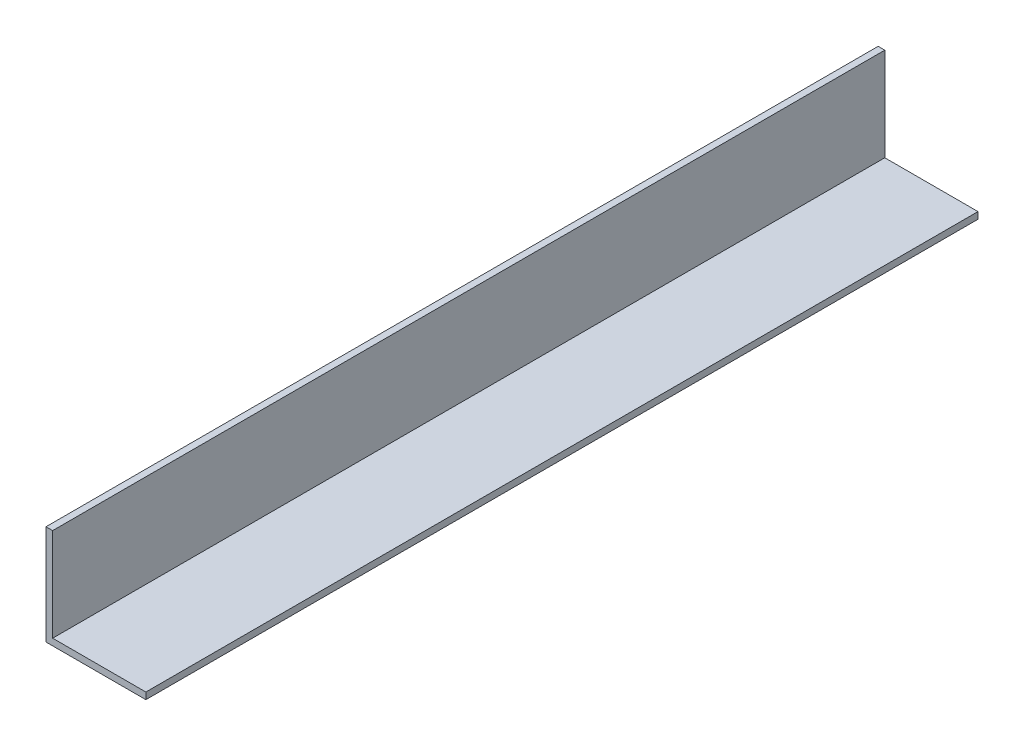
SolidWorks part; units mm, degrees
ref_plane "Front Plane" through (0, 0, 0) normal (0, 0, 1) x (1, 0, 0)
ref_plane "Top Plane" through (0, 0, 0) normal (0, 1, 0) x (1, 0, 0)
ref_plane "Right Plane" through (0, 0, 0) normal (1, 0, 0) x (0, 0, -1)
sketch "Sketch1" plane through (0, 0, 0) normal (0, 0, 1) x (1, 0, 0)
  line L0 (0, 5.6023) -> (0, 35.6023)
  line L1 (0, 35.6023) -> (2, 35.6023)
  line L2 (2, 35.6023) -> (2, 7.6023)
  line L3 (2, 7.6023) -> (30, 7.6023)
  line L4 (30, 7.6023) -> (30, 5.6023)
  line L5 (30, 5.6023) -> (0, 5.6023)
extrude "Boss-Extrude1" add sketch "Sketch1" along normal blind 250
